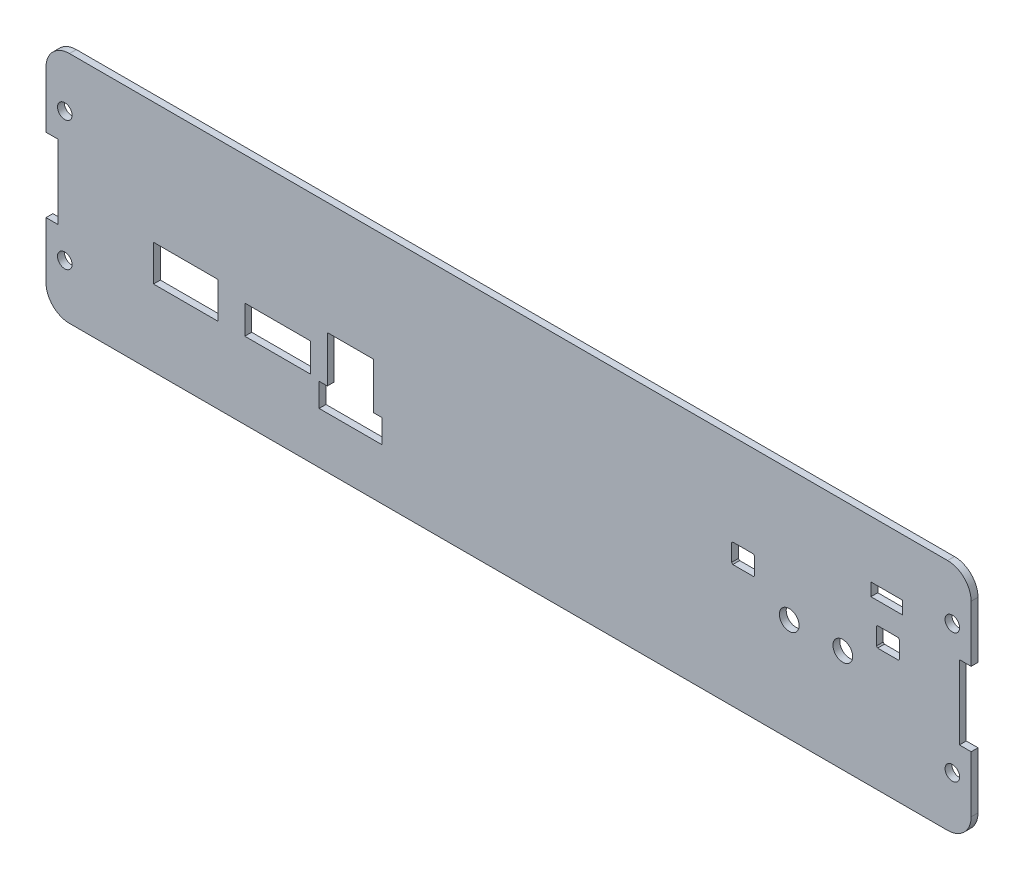
SolidWorks part; units mm, degrees
ref_plane "Front Plane" through (0, 0, 0) normal (0, 0, 1) x (1, 0, 0)
ref_plane "Top Plane" through (0, 0, 0) normal (0, 1, 0) x (1, 0, 0)
ref_plane "Right Plane" through (0, 0, 0) normal (1, 0, 0) x (0, 0, -1)
sketch "Sketch2" plane through (0, 0, 0) normal (0, 0, 1) x (1, 0, 0)
  line L0 (118.618, 31.5722) -> (-118.618, 31.5722)
  line L1 (-124.968, 25.2222) -> (-124.968, 9.9822)
  line L2 (-124.968, 9.9822) -> (-121.793, 9.9822)
  line L3 (-121.793, 9.9822) -> (-121.793, -9.9822)
  line L4 (0, 0) -> (0, 31.5722) construction
  line L5 (0, 0) -> (-121.793, 0) construction
  line L6 (124.968, 25.2222) -> (124.968, 9.9822)
  line L7 (124.968, 9.9822) -> (121.793, 9.9822)
  line L8 (121.793, 9.9822) -> (121.793, -9.9822)
  line L9 (124.968, -9.9822) -> (121.793, -9.9822)
  line L10 (124.968, -25.2222) -> (124.968, -9.9822)
  line L11 (-124.968, -9.9822) -> (-121.793, -9.9822)
  line L12 (-124.968, -25.2222) -> (-124.968, -9.9822)
  line L13 (118.618, -31.5722) -> (-118.618, -31.5722)
  arc A0 (-124.968, 25.2222) -> (-118.618, 31.5722) centre (-118.618, 25.2222) cw
  arc A1 (124.968, 25.2222) -> (118.618, 31.5722) centre (118.618, 25.2222) ccw
  arc A2 (124.968, -25.2222) -> (118.618, -31.5722) centre (118.618, -25.2222) cw
  arc A3 (-124.968, -25.2222) -> (-118.618, -31.5722) centre (-118.618, -25.2222) ccw
  point P22 (121.793, 0)
  point P25 (-124.968, -17.6022)
  dimension "D1" = 6.35
  dimension "D2" = 3.175
  dimension "D3" = 21.59
  dimension "D4" = 9.9822
  dimension "D5" = 249.936
extrude "MainBody" add sketch "Sketch2" along normal blind 1.8542
sketch "Sketch3" plane through (0, 0, 1.8542) normal (0, 0, 1) x (1, 0, 0)
  line L0 (118.618, 31.5722) -> (-118.618, 31.5722) construction
  line L2 (0, 31.5722) -> (0, 0) construction
  line L3 (0, 0) -> (-121.793, 0) construction
  line L4 (-121.793, 9.9822) -> (-121.793, -9.9822) construction
  circle A0 centre (-119.888, 17.4625) radius 1.9685
  circle A1 centre (119.888, 17.4625) radius 1.9685
  circle A2 centre (119.888, -17.4625) radius 1.9685
  circle A3 centre (-119.888, -17.4625) radius 1.9685
  dimension "D1" = 3.937
  dimension "D2" = 17.4625
  dimension "D3" = 119.888
extrude "MountHoles" cut sketch "Sketch3" against normal through all
ref_axis "MntTopLeft" through (-119.888, 17.4625, 0) along (0, 0, 1)
ref_axis "MntBottomLeft" through (-119.888, -17.4625, 0) along (0, 0, 1)
ref_axis "MntTopRight" through (119.888, 17.4625, 0) along (0, 0, 1)
ref_axis "MntBottomRight" through (119.888, -17.4625, 0) along (0, 0, 1)
ref_plane "ExtFront" through (0, 0, 1.8542) normal (0, 0, 1) x (1, 0, 0)
ref_plane "IntFront" through (0, 0, 0) normal (0, 0, -1) x (-1, 0, 0)
ref_plane "TBCenter" through (0, 0, 0) normal (0, 1, 0) x (1, 0, 0)
ref_plane "LRCenter" through (0, 0, 0) normal (-1, 0, 0) x (0, 0, 1)
sketch "Sketch4" plane through (0, 0, 1.8542) normal (0, 0, 1) x (1, 0, 0)
  line L17 (97.8918, 16.1942) -> (97.8918, 12.7469)
  line L18 (97.8918, 12.7469) -> (106.4258, 12.7469)
  line L19 (106.4258, 12.7469) -> (106.4258, 16.1942)
  line L20 (106.4258, 16.1942) -> (97.8918, 16.1942)
  line L21 (97.8918, 16.1942) -> (97.8918, 12.7469)
  line L22 (97.8918, 12.7469) -> (106.4258, 12.7469)
  line L23 (106.4258, 12.7469) -> (106.4258, 16.1942)
  line L24 (106.4258, 16.1942) -> (97.8918, 16.1942)
  line L28 (-95.9336, -1.2294) -> (-95.9336, -11.0084)
  line L29 (-95.9336, -11.0084) -> (-78.5599, -11.0084)
  line L30 (-78.5599, -11.0084) -> (-78.5599, -1.2294)
  line L31 (-78.5599, -1.2294) -> (-95.9336, -1.2294)
  line L32 (-95.9336, -1.2294) -> (-95.9336, -11.0084)
  line L33 (-95.9336, -11.0084) -> (-78.5599, -11.0084)
  line L34 (-78.5599, -11.0084) -> (-78.5599, -1.2294)
  line L35 (-78.5599, -1.2294) -> (-95.9336, -1.2294)
  line L40 (-53.4508, -10.8814) -> (-53.4508, -3.1234)
  line L41 (-71.2588, -10.8814) -> (-53.4508, -10.8814)
  line L42 (-71.2588, -3.1234) -> (-71.2588, -10.8814)
  line L43 (-53.4508, -3.1234) -> (-71.2588, -3.1234)
  line L44 (-53.4508, -10.8814) -> (-53.4508, -3.1234)
  line L45 (-71.2588, -10.8814) -> (-53.4508, -10.8814)
  line L46 (-71.2588, -3.1234) -> (-71.2588, -10.8814)
  line L47 (-53.4508, -3.1234) -> (-71.2588, -3.1234)
  line L60 (-36.4248, -11.3894) -> (-36.4248, 1.1266)
  line L61 (-34.1608, -11.3894) -> (-36.4248, -11.3894)
  line L62 (-34.1608, -17.7394) -> (-34.1608, -11.3894)
  line L63 (-51.1788, -17.7394) -> (-34.1608, -17.7394)
  line L64 (-51.1788, -11.3894) -> (-51.1788, -17.7394)
  line L65 (-48.9688, -11.3894) -> (-51.1788, -11.3894)
  line L66 (-48.9688, 1.1266) -> (-48.9688, -11.3894)
  line L67 (-36.4248, 1.1266) -> (-48.9688, 1.1266)
  line L68 (-36.4248, -11.3894) -> (-36.4248, 1.1266)
  line L69 (-34.1608, -11.3894) -> (-36.4248, -11.3894)
  line L70 (-34.1608, -17.7394) -> (-34.1608, -11.3894)
  line L71 (-51.1788, -17.7394) -> (-34.1608, -17.7394)
  line L72 (-51.1788, -11.3894) -> (-51.1788, -17.7394)
  line L73 (-48.9688, -11.3894) -> (-51.1788, -11.3894)
  line L74 (-48.9688, 1.1266) -> (-48.9688, -11.3894)
  line L75 (-36.4248, 1.1266) -> (-48.9688, 1.1266)
  line L346 (60.2488, 6.5473) -> (60.2488, 1.9462)
  line L347 (60.2488, 1.9462) -> (60.5772, 1.6179)
  line L348 (60.5772, 1.6179) -> (66.1688, 1.6179)
  line L349 (66.1688, 1.6179) -> (66.4972, 1.9462)
  line L350 (66.4972, 1.9462) -> (66.4972, 6.5473)
  line L351 (66.4972, 6.5473) -> (66.1688, 6.8757)
  line L352 (66.1688, 6.8757) -> (60.5772, 6.8757)
  line L353 (60.5772, 6.8757) -> (60.2488, 6.5473)
  line L354 (60.2488, 6.5473) -> (60.2488, 1.9462)
  line L355 (60.2488, 1.9462) -> (60.5772, 1.6179)
  line L356 (60.5772, 1.6179) -> (66.1688, 1.6179)
  line L357 (66.1688, 1.6179) -> (66.4972, 1.9462)
  line L358 (66.4972, 1.9462) -> (66.4972, 6.5473)
  line L359 (66.4972, 6.5473) -> (66.1688, 6.8757)
  line L360 (66.1688, 6.8757) -> (60.5772, 6.8757)
  line L361 (60.5772, 6.8757) -> (60.2488, 6.5473)
  line L398 (99.3648, 6.5473) -> (99.3648, 1.9462)
  line L399 (99.3648, 1.9462) -> (99.6932, 1.6179)
  line L400 (99.6932, 1.6179) -> (105.2848, 1.6179)
  line L401 (105.2848, 1.6179) -> (105.6132, 1.9462)
  line L402 (105.6132, 1.9462) -> (105.6132, 6.5473)
  line L403 (105.6132, 6.5473) -> (105.2848, 6.8757)
  line L404 (105.2848, 6.8757) -> (99.6932, 6.8757)
  line L405 (99.6932, 6.8757) -> (99.3648, 6.5473)
  line L406 (99.3648, 6.5473) -> (99.3648, 1.9462)
  line L407 (99.3648, 1.9462) -> (99.6932, 1.6179)
  line L408 (99.6932, 1.6179) -> (105.2848, 1.6179)
  line L409 (105.2848, 1.6179) -> (105.6132, 1.9462)
  line L410 (105.6132, 1.9462) -> (105.6132, 6.5473)
  line L411 (105.6132, 6.5473) -> (105.2848, 6.8757)
  line L412 (105.2848, 6.8757) -> (99.6932, 6.8757)
  line L413 (99.6932, 6.8757) -> (99.3648, 6.5473)
  circle A57 centre (90.297, -3.7295) radius 2.667
  circle A58 centre (90.297, -3.7295) radius 2.667
  circle A60 centre (75.819, -3.7295) radius 2.667
  circle A73 centre (75.819, -3.7295) radius 2.667
  point P0 (0, 0)
  dimension "D5" = 0.254
  dimension "D6" = 0.254
  dimension "D7" = 0.254
  dimension "D8" = 0.254
  dimension "D3" = 0.254
extrude "PanelCutout" cut sketch "Sketch4" against normal up to next
equation "\"MainBodyExtWidth\"=9.84"
equation "\"MainBodyExtHeight\"=2.52"
equation "\"D4@Sketch2\"=0.786/2in"
equation "\"D5@Sketch2\"=\"MainBodyExtWidth\""
equation "\"MainBodyThickness\"= 0.073"
equation "\"D1@MainBody\" = \"MainBodyThickness\""
equation "\"ScrewMountSize\"=0.155"
equation "\"D1@Sketch3\"=\"ScrewMountSize\""
equation "\"Tolerance\"=0.01"
equation "\"D5@Sketch4\"=\"Tolerance\""
equation "\"D8@Sketch4\"=\"Tolerance\""
equation "\"D6@Sketch4\"=\"Tolerance\""
equation "\"D7@Sketch4\"=\"Tolerance\""
equation "\"D4@Sketch4\"=\"Tolerance\""
equation "\"D3@Sketch4\"=\"Tolerance\""
equation "\"D1@Sketch4\"=\"Tolerance\""
equation "\"D2@Sketch4\"=\"Tolerance\""
